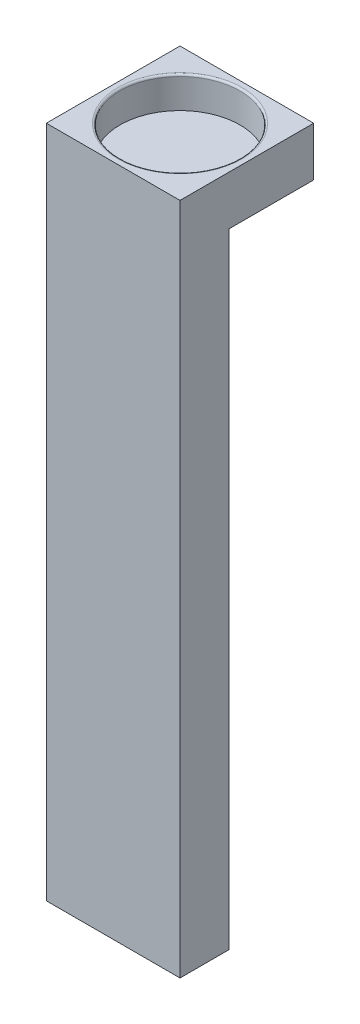
SolidWorks part; units mm, degrees
ref_plane "Front Plane" through (0, 0, 0) normal (0, 0, 1) x (1, 0, 0)
ref_plane "Top Plane" through (0, 0, 0) normal (0, 1, 0) x (1, 0, 0)
ref_plane "Right Plane" through (0, 0, 0) normal (1, 0, 0) x (0, 0, -1)
sketch "Sketch1" plane through (0, 0, 0) normal (0, 1, 0) x (1, 0, 0)
  line L1 (-6.8, 6.8) -> (6.8, 6.8)
  line L2 (-6.8, 6.8) -> (-6.8, -6.8)
  line L3 (-6.8, -6.8) -> (6.8, -6.8)
  line L4 (6.8, 6.8) -> (6.8, -6.8)
  line L5 (-6.8, 6.8) -> (6.8, -6.8) construction
  line L6 (-6.8, -6.8) -> (6.8, 6.8) construction
  point P0 (0, 0)
  dimension "D1" = 13.6
  dimension "D2" = 13.6
extrude "Boss-Extrude1" add sketch "Sketch1" along normal blind 5
sketch "Sketch2" plane through (0, 5, 0) normal (0, 1, 0) x (1, 0, 0)
  circle A0 centre (0, 0) radius 6.1
  dimension "D1" = 12.2
extrude "Cut-Extrude1" cut sketch "Sketch2" against normal blind 3.2
sketch "Sketch3" plane through (0, 0, 0) normal (0, -1, 0) x (1, 0, 0)
  line L0 (6.8, 6.8) -> (6.8, -6.8) construction
  line L1 (-6.8, 6.8) -> (6.8, 6.8)
  line L2 (-6.8, 6.8) -> (-6.8, 1.8)
  line L3 (-6.8, 1.8) -> (6.8, 1.8)
  line L4 (6.8, 6.8) -> (6.8, 1.8)
  dimension "D1" = 5
extrude "Boss-Extrude2" add sketch "Sketch3" along normal blind 63.5
sketch "Sketch4" plane through (0, 1.8, 0) normal (0, 1, 0) x (1, 0, 0)
  point P0 (0, 0)
fillet "Fillet1" radius 0.2 1 edges at (0, 5, 6.1)
